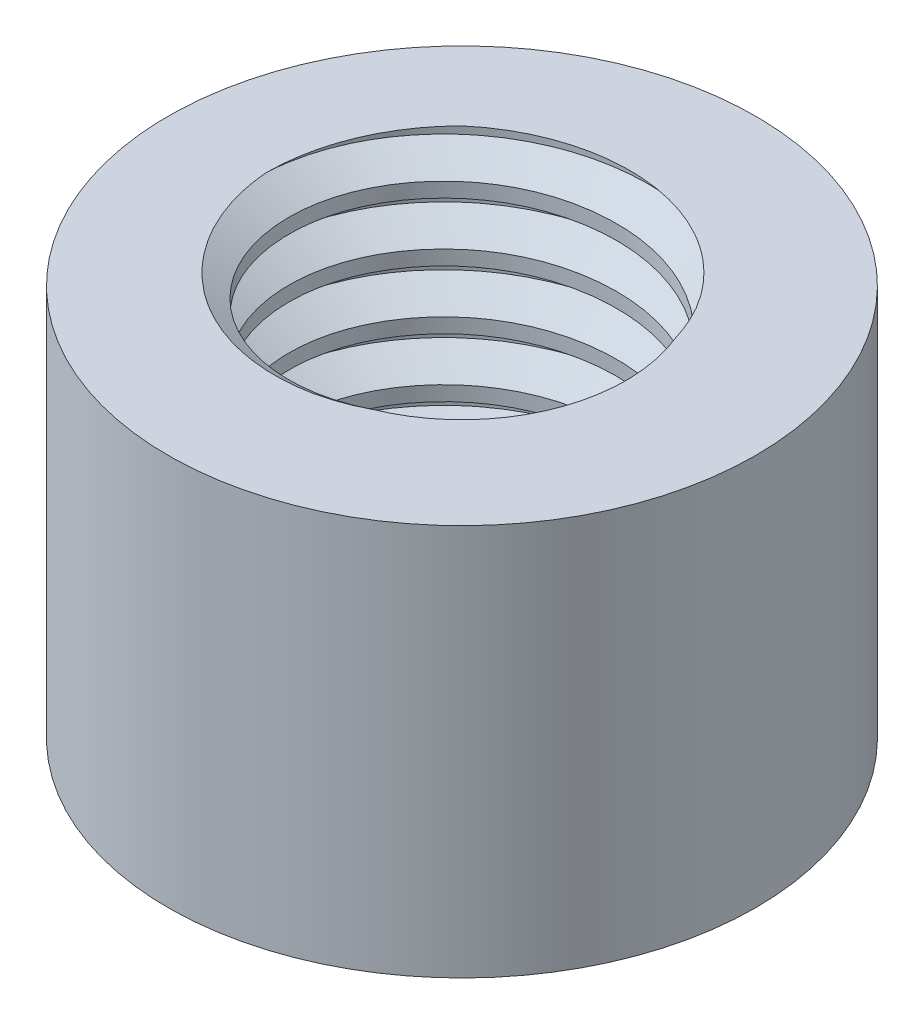
SolidWorks part; units mm, degrees
ref_plane "Alzado" through (0, 0, 0) normal (0, 0, 1) x (1, 0, 0)
ref_plane "Planta" through (0, 0, 0) normal (0, 1, 0) x (1, 0, 0)
ref_plane "Vista lateral" through (0, 0, 0) normal (1, 0, 0) x (0, 0, -1)
sketch "Croquis1" plane through (0, 0, 0) normal (0, 0, 1) x (1, 0, 0)
  line L0 (-5, 0) -> (-7.5, 0)
  line L1 (-7.5, 0) -> (-7.5, -5)
  line L3 (-7.5, -5) -> (-7.5, -10)
  line L4 (-7.5, -10) -> (0, -10)
  line L5 (0, -10) -> (0, -8)
  line L6 (-5, 0) -> (-5, -8)
  line L7 (-5, -8) -> (0, -8)
  dimension "D1" = 8
  dimension "D2" = 5
  dimension "D3" = 7.5
  dimension "D4" = 5
  dimension "D5" = 5
revolve "Revolución1" add sketch "Croquis1" angle 360 about L5
thread "Rosca1" pitch 1.5 method extrude profile "Perfil de rosca1" start angle 0, offset 1.5, length 0, pitch 1.5, diameter 10
ref_plane "Plano1" through (-5, 1.5, 0) normal (0, 0, 1) x (-1, 0, 0)
sketch "Perfil de rosca1" plane through (-5, 1.5, 0) normal (0, 0, 1) x (-1, 0, 0)
  line L0 (0, 0) -> (0, 1.5) construction
  line L11 (0, 0) -> (0, 1.3125)
  line L12 (0, 1.3125) -> (-0.8119, 0.8437)
  line L13 (-0.8119, 0.8437) -> (-0.8119, 0.4687)
  line L15 (-0.8119, 0.4687) -> (0, 0)
  line L17 (-0.8119, 0.6562) -> (0, 0.6562) construction
  point P2 (0, 0)
  dimension "Pitch" = 1.5
  dimension "Profile_Angle" = 60
  dimension "Profile_Land" = 0.375
  dimension "Profile_Height" = 0.8119
sketch "Croquis5" plane through (0, 0, 0) normal (0, 1, 0) x (1, 0, 0)
  circle A0 centre (0, 0) radius 7.5
extrude "Cortar-Extruir1" cut sketch "Croquis5" along normal blind 10
sketch "Croquis4" plane through (0, -8, 0) normal (0, -1, 0) x (1, 0, 0)
  line L0 (-141.5039, -246.875) -> (-141.5039, -34.875) construction
  line L1 (-138.3656, -237.2134) -> (-138.3656, -25.2134) construction
  line L2 (3.5019, -1.9637) -> (2.8067, -1.7469)
  line L3 (6.7492, -1.63) -> (6.7492, 0.4013) construction
  circle A0 centre (0, 0) radius 7.5 construction
  spline S0 degree 3 poles (5.4783, -3.0026) (5.2939, -3.0997) (4.9059, -2.8843) (4.5014, -2.7858) (4.1969, -2.6771) (3.9677, -2.5968) (3.7603, -2.583) (3.586, -2.5795) (3.4419, -2.7495) (2.7807, -3.1745) (0.8489, -3.9586) (-1.7314, -3.2995) (-3.143, -1.6045) (-4.1204, 0.1202) (-4.8068, 1.6146) (-5.2997, 2.5812) knots 0 0 0 0 0.045509 0.074889 0.092461 0.113664 0.125695 0.137175 0.148043 0.170271 0.305001 0.581101 0.650984 0.7701 1 1 1 1
  spline S1 degree 3 poles (-5.2997, 2.5812) (-4.6157, 2.7162) (-3.265, 2.754) (-0.5305, 2.721) (2.2876, 1.5473) (3.6836, -0.6599) (4.0278, -1.7191) (3.8973, -2.2471) (4.1019, -2.3029) (4.2825, -2.3865) (4.5592, -2.4756) (4.9567, -2.6175) (5.5058, -2.7047) (5.4783, -3.0026) knots 0 0 0 0 0.154785 0.300688 0.611266 0.783841 0.856255 0.872093 0.881128 0.897547 0.918952 0.943746 1 1 1 1
  spline S2 degree 3 poles (3.1974, -2.4352) (2.9687, -2.7045) (2.312, -3.0014) (1.6373, -3.2496) (1.2596, -3.2365) knots 0 0 0 0 0.481114 1 1 1 1
  spline S3 degree 1 poles (3.1974, -2.4352) (2.7927, -2.2546) knots 0 0 1 1
  spline S4 degree 3 poles (2.7927, -2.2546) (2.6241, -2.3497) (2.3856, -2.5367) (1.85, -2.8253) (1.4697, -3.0048) (1.2596, -3.2365) knots 0 0 0 0 0.317739 0.494985 1 1 1 1
  spline S5 degree 3 poles (3.5019, -1.9637) (3.5448, -1.674) (3.479, -1.2338) (3.1676, -0.5653) (2.9266, -0.1902) (2.7588, 0.0631) knots 0 0 0 0 0.395874 0.586576 1 1 1 1
  spline S6 degree 3 poles (2.7588, 0.0631) (2.7118, -0.261) (2.7882, -0.8634) (2.7647, -1.4686) (2.8067, -1.7469) knots 0 0 0 0 0.536589 1 1 1 1
  spline S7 degree 3 poles (2.3326, -2.0574) (2.2044, -2.2378) (1.909, -2.4192) (1.5011, -2.7059) (1.0756, -2.9003) (0.8303, -3.1358) (0.6574, -3.2005) knots 0 0 0 0 0.316444 0.507916 0.734242 1 1 1 1
  spline S8 degree 3 poles (0.6574, -3.2005) (0.275, -3.2819) (-0.1224, -3.2165) (-0.488, -3.0946) knots 0 0 0 0 1 1 1 1
  spline S9 degree 3 poles (-0.488, -3.0946) (-0.3118, -2.9094) (0.0121, -2.6557) (0.488, -2.3296) (0.9313, -2.0449) (1.2168, -1.8054) (1.3936, -1.7022) knots 0 0 0 0 0.326234 0.525 0.738479 1 1 1 1
  spline S10 degree 3 poles (2.3326, -2.0574) (2.1712, -2.0169) (1.8613, -1.8893) (1.5526, -1.7596) (1.3936, -1.7022) knots 0 0 0 0 0.495129 1 1 1 1
  spline S11 degree 3 poles (2.4463, -1.4679) (2.1602, -1.3858) (1.8851, -1.2699) (1.6149, -1.1462) knots 0 0 0 0 1 1 1 1
  spline S12 degree 3 poles (1.6149, -1.1462) (1.6211, -0.8204) (1.4845, -0.3144) (1.4411, 0.4808) (1.3806, 0.9503) (1.3936, 1.227) knots 0 0 0 0 0.405946 0.652936 1 1 1 1
  spline S13 degree 3 poles (2.4463, -1.4679) (2.4297, -1.1969) (2.4007, -0.583) (2.3637, 0.0306) (2.3326, 0.3724) knots 0 0 0 0 0.441733 1 1 1 1
  spline S14 degree 3 poles (2.3326, 0.3724) (2.294, 0.5532) (2.0913, 0.7421) (1.7933, 1.0664) (1.531, 1.1474) (1.3936, 1.227) knots 0 0 0 0 0.397173 0.631475 1 1 1 1
  spline S15 degree 3 poles (0.8942, -1.4679) (0.6937, -1.6252) (0.3522, -1.8797) (-0.0722, -2.2464) (-0.5217, -2.4886) (-0.7478, -2.7452) (-0.9161, -2.858) knots 0 0 0 0 0.334549 0.559859 0.734194 1 1 1 1
  spline S16 degree 3 poles (-0.9161, -2.858) (-1.1399, -2.8474) (-1.4251, -2.6065) (-1.7638, -2.4555) (-1.8736, -2.3379) knots 0 0 0 0 0.568618 1 1 1 1
  spline S17 degree 3 poles (0.8942, -1.4679) (0.7162, -1.3644) (0.3037, -1.2371) (-0.0231, -0.9544) (-0.2084, -0.8427) knots 0 0 0 0 0.486655 1 1 1 1
  spline S18 degree 3 poles (-1.8736, -2.3379) (-1.7031, -2.1696) (-1.2004, -1.6133) (-0.5531, -1.2169) (-0.2084, -0.8427) knots 0 0 0 0 0.321358 1 1 1 1
  spline S19 degree 3 poles (-0.7366, -0.6125) (-0.8374, -0.8429) (-1.1429, -1.093) (-1.7041, -1.5013) (-1.9371, -1.9063) (-2.2093, -2.0574) knots 0 0 0 0 0.350602 0.564021 1 1 1 1
  spline S20 degree 3 poles (-2.2093, -2.0574) (-2.4128, -1.9247) (-2.6083, -1.5393) (-2.9064, -1.2329) (-3.007, -1.0685) knots 0 0 0 0 0.548239 1 1 1 1
  spline S21 degree 3 poles (-3.007, -1.0685) (-2.7766, -0.9212) (-2.453, -0.7138) (-1.9974, -0.3665) (-1.7257, -0.2309) (-1.5957, -0.0909) knots 0 0 0 0 0.477748 0.66972 1 1 1 1
  spline S22 degree 3 poles (-0.7366, -0.6125) (-0.9987, -0.3959) (-1.3491, -0.3293) (-1.5957, -0.0909) knots 0 0 0 0 1 1 1 1
  spline S23 degree 3 poles (-3.1948, -0.7518) (-2.9653, -0.5263) (-2.5219, -0.351) (-2.0837, -0.0432) (-2.0218, 0.1404) knots 0 0 0 0 0.616737 1 1 1 1
  spline S24 degree 3 poles (-3.1948, -0.7518) (-3.3879, -0.5328) (-3.5151, -0.0639) (-3.792, 0.3277) (-3.8787, 0.4982) knots 0 0 0 0 0.597562 1 1 1 1
  spline S25 degree 3 poles (-3.8787, 0.4982) (-3.5903, 0.523) (-3.45, 0.9435) (-3.145, 0.8692) knots 0 0 0 0 1 1 1 1
  spline S26 degree 3 poles (-2.0218, 0.1404) (-2.3504, 0.4588) (-2.8239, 0.5402) (-3.145, 0.8692) knots 0 0 0 0 1 1 1 1
  spline S27 degree 3 poles (-3.5481, 1.1472) (-3.6438, 1.1098) (-3.9259, 0.7264) (-4.1677, 1.0126) (-4.332, 1.3708) (-4.5106, 1.6961) (-4.6305, 1.9248) knots 0 0 0 0 0.310868 0.394958 0.558357 1 1 1 1
  spline S28 degree 3 poles (-3.5481, 1.1472) (-3.6972, 1.2876) (-4.0477, 1.5622) (-4.4009, 1.8394) (-4.6305, 1.9248) knots 0 0 0 0 0.458358 1 1 1 1
  spline S29 degree 3 poles (-3.4575, 1.6984) (-3.4446, 1.8696) (-3.4675, 2.0387) (-3.448, 2.3872) (-3.6524, 2.3818) (-3.8288, 2.4231) (-4.1502, 2.3868) (-4.3925, 2.4738) (-4.5626, 2.4185) knots 0 0 0 0 0.268265 0.385213 0.459279 0.566834 0.712658 1 1 1 1
  spline S30 degree 3 poles (-3.4575, 1.6984) (-3.6626, 1.8217) (-4.0434, 2.0449) (-4.3804, 2.3307) (-4.5626, 2.4185) knots 0 0 0 0 0.544609 1 1 1 1
  spline S31 degree 3 poles (-1.9071, 0.7093) (-2.1368, 0.7834) (-2.3761, 1.0401) (-2.8146, 1.1693) (-2.9573, 1.4734) (-3.0183, 1.8581) (-3.0616, 2.1728) (-3.0616, 2.3642) knots 0 0 0 0 0.312979 0.470055 0.574114 0.74199 1 1 1 1
  spline S32 degree 3 poles (-1.9071, 0.7093) (-2.0023, 0.9795) (-1.9569, 1.3762) (-2.1088, 1.8597) (-2.2019, 2.1042) (-2.2441, 2.3369) (-2.5907, 2.4073) (-2.826, 2.3281) (-3.0616, 2.3642) knots 0 0 0 0 0.341457 0.475561 0.607155 0.678259 0.727851 1 1 1 1
  spline S33 degree 3 poles (-0.6749, 0) (-0.8573, 0.0994) (-1.0994, 0.2038) (-1.389, 0.4007) (-1.5243, 0.6723) (-1.613, 1.0358) (-1.5993, 1.6148) (-1.8272, 1.9939) (-1.828, 2.2736) knots 0 0 0 0 0.225465 0.291568 0.375328 0.547817 0.698545 1 1 1 1
  spline S34 degree 3 poles (-0.6749, 0) (-0.6758, 0.2749) (-0.8461, 0.6671) (-0.8655, 1.2155) (-0.9551, 1.6206) (-0.9955, 1.9176) (-1.0252, 2.2142) (-1.4123, 2.234) (-1.6149, 2.3137) (-1.828, 2.2736) knots 0 0 0 0 0.271622 0.416103 0.548394 0.680553 0.734696 0.811447 1 1 1 1
  spline S35 degree 3 poles (1.113, -0.8427) (0.903, -0.7713) (0.5455, -0.6815) (0.1628, -0.4104) (-0.161, -0.3215) (-0.3407, 0.033) (-0.3278, 0.4758) (-0.5112, 1.1635) (-0.4708, 1.6819) (-0.5708, 2.0086) knots 0 0 0 0 0.180625 0.286973 0.37907 0.43135 0.590976 0.729094 1 1 1 1
  spline S36 degree 3 poles (1.113, -0.8427) (1.1252, -0.5594) (1.0712, -0.1167) (1.0193, 0.5379) (0.905, 1.0219) (0.9924, 1.5087) (0.6827, 1.6954) (0.3964, 1.8042) (-0.0493, 1.8965) (-0.3527, 2.0617) (-0.5708, 2.0086) knots 0 0 0 0 0.213489 0.340134 0.492639 0.605071 0.657073 0.746886 0.84184 1 1 1 1
  text T0 "LL" font "Unispace" height in points 9
  dimension "D1" = 15
extrude "Saliente-Extruir1" add sketch "Croquis4" along normal blind 2
